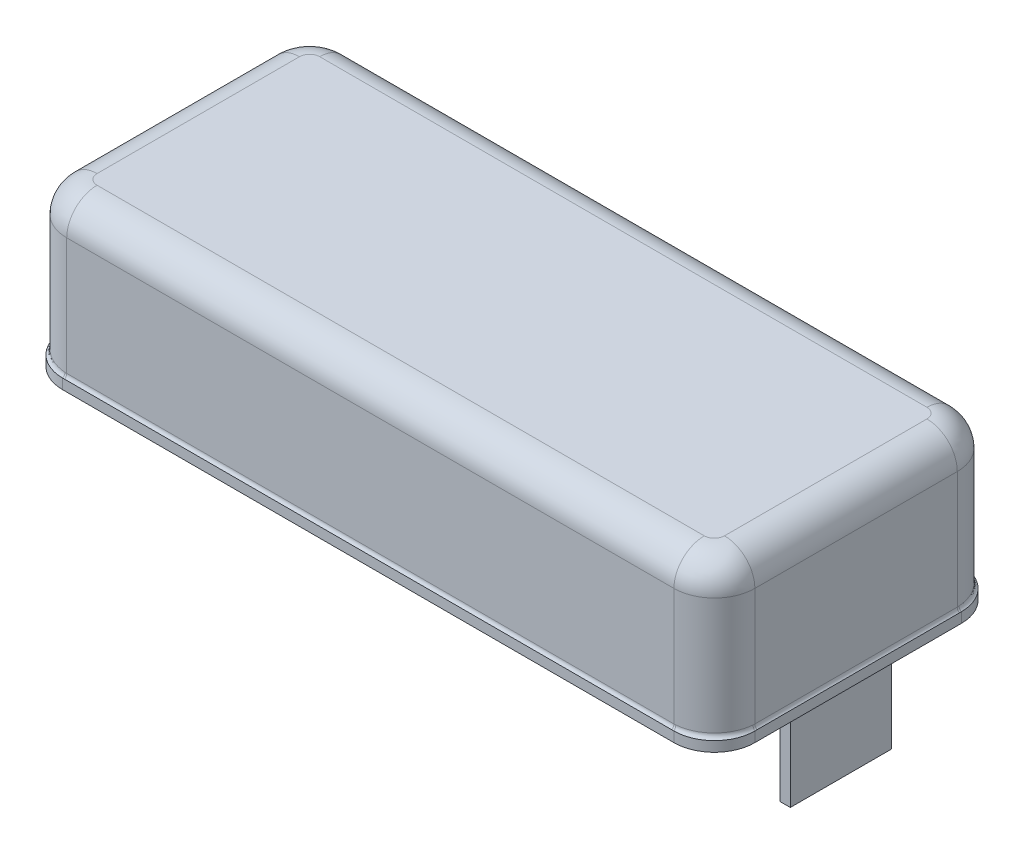
SolidWorks part; units mm, degrees
ref_plane "Front Plane" through (0, 0, 0) normal (0, 0, 1) x (1, 0, 0)
ref_plane "Top Plane" through (0, 0, 0) normal (0, 1, 0) x (1, 0, 0)
ref_plane "Right Plane" through (0, 0, 0) normal (1, 0, 0) x (0, 0, -1)
sketch "Sketch1" plane through (0, 0, 0) normal (0, 1, 0) x (1, 0, 0)
  line L1 (0, 0) -> (68, 0)
  line L2 (0, 0) -> (0, 28)
  line L3 (0, 28) -> (68, 28)
  line L4 (68, 0) -> (68, 28)
  dimension "D1" = 68
  dimension "D2" = 28
extrude "Boss-Extrude1" add sketch "Sketch1" along normal blind 16
fillet "Fillet1" radius 4 4 edges at (0, 8, -28) (68, 8, -28) (68, 8, 0) (0, 8, 0)
fillet "Fillet2" radius 3 8 edges at (1.1716, 16, -1.1716) (0, 16, -14) (1.1716, 16, -26.8284) (34, 16, -28) (66.8284, 16, -26.8284) (68, 16, -14) (66.8284, 16, -1.1716) (34, 16, 0)
sketch "Sketch2" plane through (0, 0, 0) normal (0, -1, 0) x (1, 0, 0)
  line L0 (34, 0) -> (34, -28) construction
  line L1 (4, 0) -> (64, 0) construction
  line L2 (64, -28) -> (4, -28) construction
  line L3 (38.75, -7.8) -> (48.25, -7.8) construction
  line L5 (48.25, -7.8) -> (57.75, -7.8)
  line L6 (38.75, -7.8) -> (38.75, -28) construction
  line L7 (29.25, -7.8) -> (38.75, -7.8) construction
  circle A0 centre (38.75, -7.8) radius 1.4815
  circle A1 centre (48.25, -7.8) radius 1.4
  circle A2 centre (57.75, -7.8) radius 1.4
  circle A3 centre (10.25, -7.8) radius 1.4
  circle A4 centre (19.75, -7.8) radius 1.4
  circle A5 centre (29.25, -7.8) radius 1.4815
  dimension "D2" = 9.5
  dimension "D3" = 20.2
  dimension "D1" = 9.5
  dimension "D4" = 9.5
extrude "Boss-Extrude3" add sketch "Sketch2" along normal blind 4.5 contours A3 | A4 | A5 | A0 | A1 | A2 region at (57.75, 0, -6.4396) region at (46.8896, 0, -7.8) region at (38.75, 0, -7.8) region at (10.25, 0, -7.8) region at (19.75, 0, -7.8) region at (29.25, 0, -7.8)
sketch "Sketch3" plane through (0, 0, 0) normal (0, -1, 0) x (1, 0, 0)
  line L1 (4, -28.2) -> (68.2, -28.2)
  line L4 (68.2, -15.8769) -> (68.2, -28.2)
  line L5 (68.2, -28.2) -> (68.2, 0.2)
  line L8 (61.522, 0.2) -> (68.2, 0.2)
  line L9 (61.522, 0.2) -> (-0.2, 0.2)
  line L12 (-0.2, -7.0508) -> (-0.2, 0.2)
  line L13 (-0.2, 0.2) -> (-0.2, -28.2)
  line L14 (4, -28.2) -> (-0.2, -28.2)
  line M11 (0, -4) -> (0, -24)
  arc M12 (0, -24) -> (4, -28) centre (4, -24) ccw
  line M13 (4, -28) -> (64, -28)
  arc M14 (64, -28) -> (68, -24) centre (64, -24) ccw
  line M15 (68, -24) -> (68, -4)
  arc M16 (68, -4) -> (64, 0) centre (64, -4) ccw
  line M17 (64, 0) -> (4, 0)
  arc M18 (4, 0) -> (0, -4) centre (4, -4) ccw
extrude "Boss-Extrude5" add sketch "Sketch3" against normal blind 1 contours L14 L1 L4 L5 L8 L9 L12 L13 M11 M18 M17 M16 M15 M14 M13 M12 region at (1.9, 0, -27.4594)
fillet "Fillet3" radius 4 4 edges at (-0.2, 0.5, -28.2) (68.2, 0.5, -28.2) (68.2, 0.5, 0.2) (-0.2, 0.5, 0.2)
fillet "Fillet4" radius 0.5 8 edges at (1.1716, 1, -26.8284) (0, 1, -14) (1.1716, 1, -1.1716) (34, 1, 0) (66.8284, 1, -1.1716) (68, 1, -14) (66.8284, 1, -26.8284) (34, 1, -28)
sketch "Sketch4" plane through (0, 0, 0) normal (0, -1, 0) x (1, 0, 0)
  line L0 (-0.2, -14) -> (68.2, -14) construction
  line L1 (-0.2, -24.2) -> (-0.2, -3.8) construction
  line L2 (68.2, -3.8) -> (68.2, -24.2) construction
  line L3 (-0.2, -14) -> (-0.2, -9)
  line L4 (2.5, -9) -> (1.5, -9)
  line L5 (2.5, -9) -> (2.5, -19)
  line L6 (1.5, -9) -> (1.5, -19)
  line L7 (2.5, -19) -> (1.5, -19)
  line L8 (34, 0.2) -> (34, -28.2) construction
  line L9 (3.8, 0.2) -> (64.2, 0.2) construction
  line L10 (64.2, -28.2) -> (3.8, -28.2) construction
  line L11 (65.5, -9) -> (66.5, -9)
  line L12 (66.5, -9) -> (66.5, -19)
  line L13 (65.5, -19) -> (66.5, -19)
  line L14 (65.5, -9) -> (65.5, -19)
  point P8 (2.5, -14)
  point P13 (1.5, -14)
  dimension "D1" = 2.7
  dimension "D2" = 5
  dimension "D3" = 1
extrude "Boss-Extrude6" add sketch "Sketch4" along normal blind 9 contours L11 L14 L13 L12 | L7 L5 L4 L6 region at (2, 0, -14) region at (66, 0, -14)
sketch "Sketch5" plane through (0, 0, 0) normal (0, -1, 0) x (1, 0, 0)
  line L0 (2.5, -9) -> (2.5, 0.2) construction
  line L1 (2.5, -4.4) -> (4.5, -4.4) construction
  circle A0 centre (4.5, -4.4) radius 2
extrude "Cut-Extrude1" cut sketch "Sketch5" against normal blind 9
